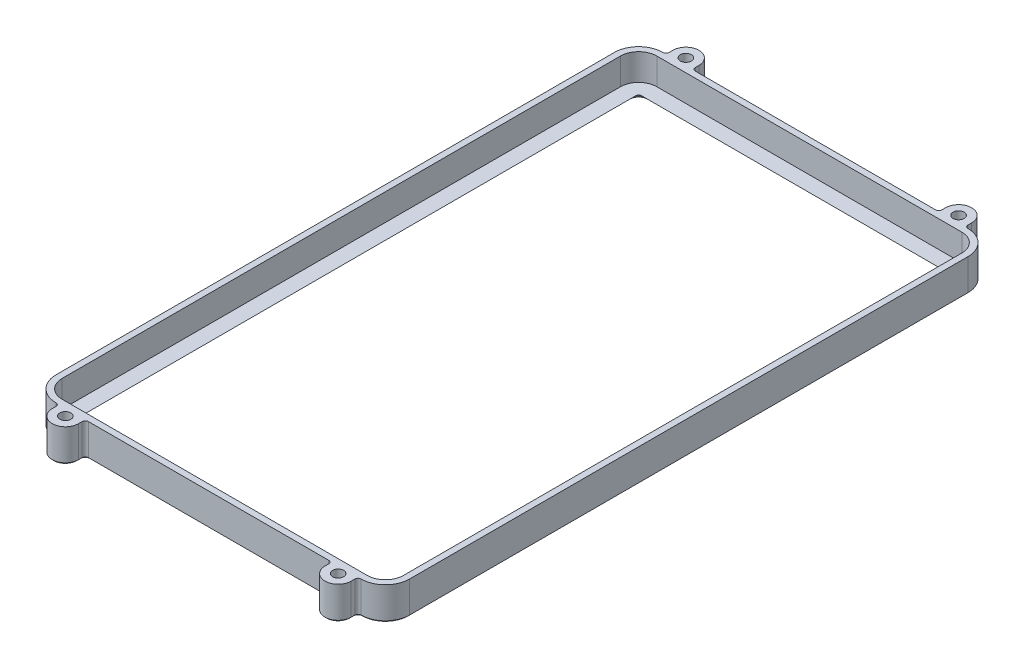
SolidWorks part; units mm, degrees
ref_plane "Front Plane" through (0, 0, 0) normal (0, 0, 1) x (1, 0, 0)
ref_plane "Top Plane" through (0, 0, 0) normal (0, 1, 0) x (1, 0, 0)
ref_plane "Right Plane" through (0, 0, 0) normal (1, 0, 0) x (0, 0, -1)
sketch "Sketch19" plane through (0, 0, 0) normal (0, 1, 0) x (-1, 0, 0)
  line L1 (-6.5603, 44.8694) -> (92.4397, 44.8694)
  line L2 (-14.4403, 36.9894) -> (-14.4403, -144.2106)
  line L3 (-6.5603, -152.0906) -> (92.4397, -152.0906)
  line L4 (100.3197, 36.9894) -> (100.3197, -144.2106)
  arc A0 (-14.4403, -144.2106) -> (-6.5603, -152.0906) centre (-6.5603, -144.2106) ccw
  arc A1 (92.4397, -152.0906) -> (100.3197, -144.2106) centre (92.4397, -144.2106) ccw
  arc A2 (100.3197, 36.9894) -> (92.4397, 44.8694) centre (92.4397, 36.9894) ccw
  arc A3 (-6.5603, 44.8694) -> (-14.4403, 36.9894) centre (-6.5603, 36.9894) ccw
  point P7 (-14.4403, -152.0906)
  point P12 (100.3197, 44.8694)
  point P15 (-14.4403, 44.8694)
  dimension "D5" = 7.88
  dimension "D3" = 114.76
  dimension "D4" = 196.96
extrude "Base" add sketch "Sketch19" along normal blind 10.64
shell "Shell" thickness 2 removed face at (-42.9397, 0, -53.6106) removed face at (-42.9397, 10.64, -53.6106)
sketch "Sketch22" plane through (0, 0, 0) normal (0, -1, 0) x (-1, 0, 0)
  line L0 (-5.5603, 154.2906) -> (-5.5603, 152.0906)
  line L1 (-6.5603, 152.0906) -> (92.4397, 152.0906) construction
  line L2 (-5.5603, 152.0906) -> (2.9397, 152.0906)
  line L3 (2.9397, 152.0906) -> (2.9397, 154.2906)
  line L4 (82.9397, 154.2906) -> (82.9397, 152.0906)
  line L5 (82.9397, 152.0906) -> (91.4397, 152.0906)
  line L6 (91.4397, 152.0906) -> (91.4397, 154.2906)
  line L7 (-5.5603, -47.0694) -> (-5.5603, -44.8694)
  line L8 (92.4397, -44.8694) -> (-6.5603, -44.8694) construction
  line L9 (-5.5603, -44.8694) -> (2.9397, -44.8694)
  line L10 (2.9397, -44.8694) -> (2.9397, -47.0694)
  line L11 (82.9397, -47.0694) -> (82.9397, -44.8694)
  line L12 (82.9397, -44.8694) -> (91.4397, -44.8694)
  line L13 (91.4397, -44.8694) -> (91.4397, -47.0694)
  line L14 (-14.4403, -36.9894) -> (-14.4403, 144.2106) construction
  line L15 (100.3197, 144.2106) -> (100.3197, -36.9894) construction
  arc A0 (-5.5603, 154.2906) -> (2.9397, 154.2906) centre (-1.3103, 154.2906) cw
  arc A1 (82.9397, 154.2906) -> (91.4397, 154.2906) centre (87.1897, 154.2906) cw
  arc A2 (-5.5603, -47.0694) -> (2.9397, -47.0694) centre (-1.3103, -47.0694) ccw
  arc A3 (82.9397, -47.0694) -> (91.4397, -47.0694) centre (87.1897, -47.0694) ccw
  dimension "D1" = 8.88
  dimension "D2" = 8.88
  dimension "D3" = 2.2
  dimension "D4" = 8.5
extrude "Clamps" add sketch "Sketch22" against normal up to surface (10.64 mm away) up to face at (-42.9397, 10.64, -53.6106)
fillet "Clamp Fillets" radius 1 8 edges at (-82.9397, 5.32, 44.8694) (5.5603, 5.32, 44.8694) (-2.9397, 5.32, 44.8694) (-91.4397, 5.32, 44.8694) (-2.9397, 5.32, -152.0906) (-91.4397, 5.32, -152.0906) (-82.9397, 5.32, -152.0906) (5.5603, 5.32, -152.0906)
sketch "Sketch25" plane through (0, 0, 0) normal (0, -1, 0) x (1, 0, 0)
  line L24 (14.4403, -144.2106) -> (14.4403, 36.9894)
  line L25 (5.5603, 45.8694) -> (5.5603, 47.0694)
  line L26 (-2.9397, 47.0694) -> (-2.9397, 45.8694)
  line L27 (-3.9397, 44.8694) -> (-81.9397, 44.8694)
  line L28 (-82.9397, 45.8694) -> (-82.9397, 47.0694)
  line L29 (-91.4397, 47.0694) -> (-91.4397, 45.8694)
  line L30 (-100.3197, 36.9894) -> (-100.3197, -144.2106)
  line L31 (-91.4397, -153.0906) -> (-91.4397, -154.2906)
  line L32 (-82.9397, -154.2906) -> (-82.9397, -153.0906)
  line L33 (-81.9397, -152.0906) -> (-3.9397, -152.0906)
  line L34 (-2.9397, -153.0906) -> (-2.9397, -154.2906)
  line L35 (5.5603, -154.2906) -> (5.5603, -153.0906)
  line L36 (14.4403, -144.2106) -> (14.4403, 36.9894)
  line L37 (5.5603, 45.8694) -> (5.5603, 47.0694)
  line L38 (-2.9397, 47.0694) -> (-2.9397, 45.8694)
  line L39 (-3.9397, 44.8694) -> (-81.9397, 44.8694)
  line L40 (-82.9397, 45.8694) -> (-82.9397, 47.0694)
  line L41 (-91.4397, 47.0694) -> (-91.4397, 45.8694)
  line L42 (-100.3197, 36.9894) -> (-100.3197, -144.2106)
  line L43 (-91.4397, -153.0906) -> (-91.4397, -154.2906)
  line L44 (-82.9397, -154.2906) -> (-82.9397, -153.0906)
  line L45 (-81.9397, -152.0906) -> (-3.9397, -152.0906)
  line L46 (-2.9397, -153.0906) -> (-2.9397, -154.2906)
  line L47 (5.5603, -154.2906) -> (5.5603, -153.0906)
  line L48 (6.5603, 37.8694) -> (-92.4397, 37.8694)
  line L49 (-93.3197, 36.9894) -> (-93.3197, -144.2106)
  line L50 (7.4403, -144.2106) -> (7.4403, 36.9894)
  line L51 (-92.4397, -145.0906) -> (6.5603, -145.0906)
  line L52 (6.5603, 37.8694) -> (-92.4397, 37.8694)
  line L53 (-93.3197, 36.9894) -> (-93.3197, -144.2106)
  line L54 (7.4403, -144.2106) -> (7.4403, 36.9894)
  line L55 (-92.4397, -145.0906) -> (6.5603, -145.0906)
  arc A4 (7.4403, 36.9894) -> (6.5603, 37.8694) centre (6.5603, 36.9894) ccw
  arc A5 (7.4403, 36.9894) -> (6.5603, 37.8694) centre (6.5603, 36.9894) ccw
  arc A6 (-92.4397, 37.8694) -> (-93.3197, 36.9894) centre (-92.4397, 36.9894) ccw
  arc A7 (-92.4397, 37.8694) -> (-93.3197, 36.9894) centre (-92.4397, 36.9894) ccw
  arc A8 (6.5603, -145.0906) -> (7.4403, -144.2106) centre (6.5603, -144.2106) ccw
  arc A9 (6.5603, -145.0906) -> (7.4403, -144.2106) centre (6.5603, -144.2106) ccw
  arc A10 (-93.3197, -144.2106) -> (-92.4397, -145.0906) centre (-92.4397, -144.2106) ccw
  arc A11 (-93.3197, -144.2106) -> (-92.4397, -145.0906) centre (-92.4397, -144.2106) ccw
  arc A24 (5.5603, 45.8694) -> (6.5603, 44.8694) centre (6.5603, 45.8694) ccw
  arc A25 (5.5603, 45.8694) -> (6.5603, 44.8694) centre (6.5603, 45.8694) ccw
  arc A26 (-92.4397, 44.8694) -> (-91.4397, 45.8694) centre (-92.4397, 45.8694) ccw
  arc A27 (-92.4397, 44.8694) -> (-91.4397, 45.8694) centre (-92.4397, 45.8694) ccw
  arc A28 (-91.4397, -153.0906) -> (-92.4397, -152.0906) centre (-92.4397, -153.0906) ccw
  arc A29 (-91.4397, -153.0906) -> (-92.4397, -152.0906) centre (-92.4397, -153.0906) ccw
  arc A30 (6.5603, -152.0906) -> (5.5603, -153.0906) centre (6.5603, -153.0906) ccw
  arc A31 (6.5603, -152.0906) -> (5.5603, -153.0906) centre (6.5603, -153.0906) ccw
  arc A32 (6.5603, -152.0906) -> (14.4403, -144.2106) centre (6.5603, -144.2106) ccw
  arc A33 (14.4403, 36.9894) -> (6.5603, 44.8694) centre (6.5603, 36.9894) ccw
  arc A35 (5.5603, 47.0694) -> (-2.9397, 47.0694) centre (1.3103, 47.0694) ccw
  arc A36 (-3.9397, 44.8694) -> (-2.9397, 45.8694) centre (-3.9397, 45.8694) ccw
  arc A37 (-82.9397, 45.8694) -> (-81.9397, 44.8694) centre (-81.9397, 45.8694) ccw
  arc A38 (-82.9397, 47.0694) -> (-91.4397, 47.0694) centre (-87.1897, 47.0694) ccw
  arc A40 (-92.4397, 44.8694) -> (-100.3197, 36.9894) centre (-92.4397, 36.9894) ccw
  arc A41 (-100.3197, -144.2106) -> (-92.4397, -152.0906) centre (-92.4397, -144.2106) ccw
  arc A43 (-91.4397, -154.2906) -> (-82.9397, -154.2906) centre (-87.1897, -154.2906) ccw
  arc A44 (-81.9397, -152.0906) -> (-82.9397, -153.0906) centre (-81.9397, -153.0906) ccw
  arc A45 (-2.9397, -153.0906) -> (-3.9397, -152.0906) centre (-3.9397, -153.0906) ccw
  arc A46 (-2.9397, -154.2906) -> (5.5603, -154.2906) centre (1.3103, -154.2906) ccw
  arc A48 (6.5603, -152.0906) -> (14.4403, -144.2106) centre (6.5603, -144.2106) ccw
  arc A49 (14.4403, 36.9894) -> (6.5603, 44.8694) centre (6.5603, 36.9894) ccw
  arc A51 (5.5603, 47.0694) -> (-2.9397, 47.0694) centre (1.3103, 47.0694) ccw
  arc A52 (-3.9397, 44.8694) -> (-2.9397, 45.8694) centre (-3.9397, 45.8694) ccw
  arc A53 (-82.9397, 45.8694) -> (-81.9397, 44.8694) centre (-81.9397, 45.8694) ccw
  arc A54 (-82.9397, 47.0694) -> (-91.4397, 47.0694) centre (-87.1897, 47.0694) ccw
  arc A56 (-92.4397, 44.8694) -> (-100.3197, 36.9894) centre (-92.4397, 36.9894) ccw
  arc A57 (-100.3197, -144.2106) -> (-92.4397, -152.0906) centre (-92.4397, -144.2106) ccw
  arc A59 (-91.4397, -154.2906) -> (-82.9397, -154.2906) centre (-87.1897, -154.2906) ccw
  arc A60 (-81.9397, -152.0906) -> (-82.9397, -153.0906) centre (-81.9397, -153.0906) ccw
  arc A61 (-2.9397, -153.0906) -> (-3.9397, -152.0906) centre (-3.9397, -153.0906) ccw
  arc A62 (-2.9397, -154.2906) -> (5.5603, -154.2906) centre (1.3103, -154.2906) ccw
  dimension "D1" = 0
  dimension "D2" = 5
extrude "Frame" add sketch "Sketch25" against normal blind 2
chamfer "Frame Chamfer" distance 2 angle 45 8 edges at (-42.9397, 0, 37.8694) (7.4403, 0, -53.6106) (-42.9397, 0, -145.0906) (-93.3197, 0, -53.6106) (7.1825, 0, 37.6116) (7.1825, 0, -144.8329) (-93.062, 0, 37.6116) (-93.062, 0, -144.8329)
sketch "Sketch23" plane through (0, 0, 0) normal (0, -1, 0) x (-1, 0, 0)
  circle A0 centre (-1.3103, 154.2906) radius 1.8
  circle A1 centre (87.1897, 154.2906) radius 1.8
  circle A2 centre (-1.3103, -47.0694) radius 1.8
  circle A3 centre (87.1897, -47.0694) radius 1.8
  arc A4 (2.9397, 154.2906) -> (-5.5603, 154.2906) centre (-1.3103, 154.2906) ccw construction
  arc A5 (91.4397, 154.2906) -> (82.9397, 154.2906) centre (87.1897, 154.2906) ccw construction
  arc A6 (-5.5603, -47.0694) -> (2.9397, -47.0694) centre (-1.3103, -47.0694) ccw construction
  arc A7 (82.9397, -47.0694) -> (91.4397, -47.0694) centre (87.1897, -47.0694) ccw construction
  dimension "D1" = 3.6
extrude "Clamp Holes" cut sketch "Sketch23" against normal through all
sketch "Sketch24" plane through (0, 0, 0) normal (0, -1, 0) x (1, 0, 0)
  circle A0 centre (-87.1897, 47.0694) radius 2.9
  circle A1 centre (1.3103, 47.0694) radius 2.9
  circle A2 centre (1.3103, -154.2906) radius 2.9
  circle A3 centre (-87.1897, -154.2906) radius 2.9
  arc A4 (-82.9397, 47.0694) -> (-91.4397, 47.0694) centre (-87.1897, 47.0694) ccw construction
  arc A5 (5.5603, 47.0694) -> (-2.9397, 47.0694) centre (1.3103, 47.0694) ccw construction
  arc A6 (-91.4397, -154.2906) -> (-82.9397, -154.2906) centre (-87.1897, -154.2906) ccw construction
  arc A7 (-2.9397, -154.2906) -> (5.5603, -154.2906) centre (1.3103, -154.2906) ccw construction
  dimension "D1" = 5.8
extrude "Clamp Countersinks" cut sketch "Sketch24" against normal blind 3.4
chamfer "Clamp Countersink Chamfers" distance 0.3 angle 45 4 edges at (-87.1897, 0, -157.1906) (1.3103, 0, -157.1906) (1.3103, 0, 44.1694) (-87.1897, 0, 44.1694)
chamfer "Shell Chamfer" distance 0.5 angle 45 28 edges at (-100.3197, 0, -53.6106) (-98.0117, 0, -149.7826) (-91.7326, 0, -152.3835) (-91.4397, 0, -153.6906) (-87.1897, 0, -158.5406) (-82.9397, 0, -153.6906) (-82.6468, 0, -152.3835) (-42.9397, 0, -152.0906) (-3.2326, 0, -152.3835) (-2.9397, 0, -153.6906) (1.3103, 0, -158.5406) (5.5603, 0, -153.6906) (5.8532, 0, -152.3835) (12.1323, 0, -149.7826) (14.4403, 0, -53.6106) (12.1323, 0, 42.5614) (5.8532, 0, 45.1623) (5.5603, 0, 46.4694) (1.3103, 0, 51.3194) (-2.9397, 0, 46.4694) (-3.2326, 0, 45.1623) (-42.9397, 0, 44.8694) (-82.6468, 0, 45.1623) (-82.9397, 0, 46.4694) (-87.1897, 0, 51.3194) (-91.4397, 0, 46.4694) (-91.7326, 0, 45.1623) (-98.0117, 0, 42.5614)
